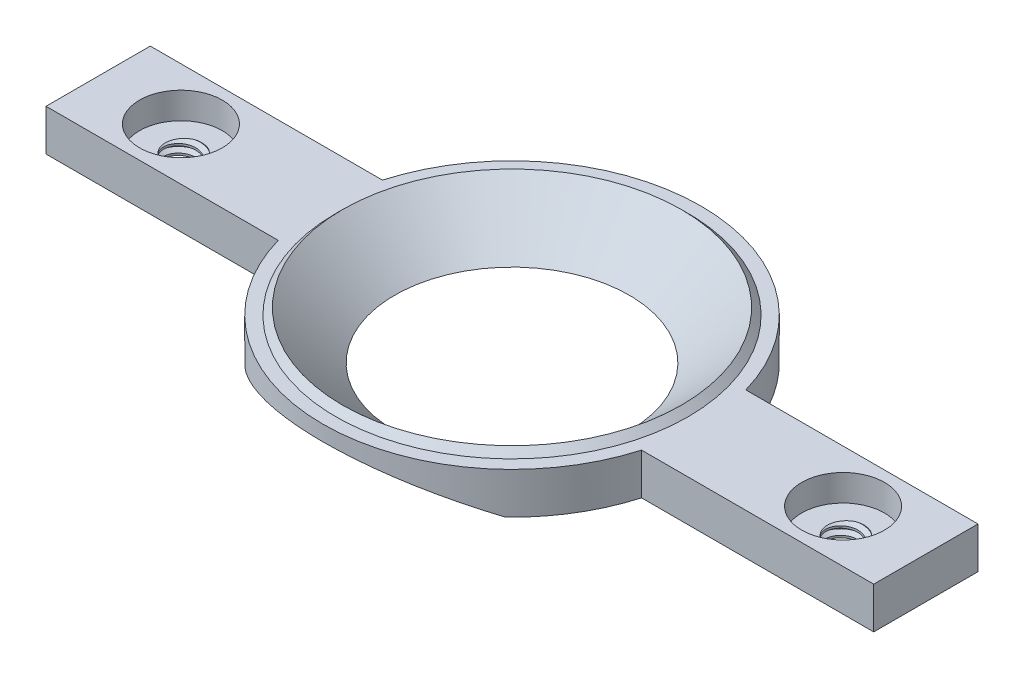
SolidWorks part; units mm, degrees
material "AISI Type 316L stainless steel"
ref_plane "Front Plane" through (0, 0, 0) normal (0, 0, 1) x (1, 0, 0)
ref_plane "Top Plane" through (0, 0, 0) normal (0, 1, 0) x (1, 0, 0)
ref_plane "Right Plane" through (0, 0, 0) normal (1, 0, 0) x (0, 0, -1)
sketch "Sketch1" plane through (0, 0, 0) normal (0, 1, 0) x (1, 0, 0)
  line L0 (0, -1000) -> (0, 49000) construction
  line L1 (-15.875, -2) -> (15.875, -2)
  line L2 (-15.875, -2) -> (-15.875, 2)
  line L3 (-15.875, 2) -> (15.875, 2)
  line L4 (15.875, -2) -> (15.875, 2)
  circle A0 centre (0, 0) radius 7.25
  circle A1 centre (0, 0) radius 6.75
  circle A2 centre (-12.7, 0) radius 0.7937
  circle A4 centre (12.7, 0) radius 0.7937
  point P4 (0, 2)
  point P6 (-15.875, 0)
  dimension "D3" = 14.5
  dimension "D4" = 0.5
  dimension "D5" = 1.5875
  dimension "D6" = 12.7
  dimension "D1" = 31.75
  dimension "D2" = 4
extrude "Boss-Extrude1" add sketch "Sketch1" along normal mid plane 1.5875 contours A0 L3 L2 L1 A2 | A1 L3 A0 L1 | A0 L0 A1 L1 | A1 L0 A0 L3 | L0 A0 L1 A1 | L0 A1 L3 A0 | A0 L1 L4 L3 A4 | A1 L1 A0 L3 region at (-4.31, 0, 5.7209) region at (0.0872, 0, 7) region at (-6.9023, 0, 0) region at (-11.4443, 0, 0) region at (11.4443, 0, 0) region at (6.9023, 0, 0) region at (-4.31, 0, -5.7209) region at (4.31, 0, -5.7209)
sketch "Sketch5" plane through (0, 0, 0) normal (0, 0, 1) x (1, 0, 0)
  line L0 (0, -1000) -> (0, 49000) construction
  line L1 (-6.7568, 0.7937) -> (-6.5, 1.0506)
  line L3 (-6.7568, 0.7937) -> (-6.7568, -0.7937)
  line L4 (-6.7568, -0.7937) -> (-5.0003, -0.7937)
  line L6 (-4.5, -0.7938) -> (-6.7568, -0.7937)
  line L7 (-6.7568, 0.7937) -> (-6.7568, -0.7937)
  line L8 (-4.5, -0.7938) -> (-5.0003, -0.7937)
  line L9 (-6.5, 1.0506) -> (-4.5, -0.7938)
  line L10 (-15.875, -0.7937) -> (-6.9687, -0.7937) construction
  line L11 (-6.7568, -0.7937) -> (-4.5, -0.7938)
  point P7 (-6.7568, 0)
  dimension "D2" = 4.5
  dimension "D3" = 135
  dimension "D4" = 6.5
  dimension "D5" = 0.3632
revolve "Revolve1" add sketch "Sketch5" angle 360 about L0 region at (-5.9861, -0.1318, 0)
sketch "Sketch6" plane through (0, 0, 0) normal (1, 0, 0) x (0, 0, -1)
  line L1 (5.25, -0.7937) -> (7.25, 0.2063)
  line L3 (0, -1000) -> (0, 49000) construction
  line L5 (0, -1000) -> (0, 49000) construction
  line L6 (-7.25, 0.2063) -> (-7.25, -0.7937)
  line L7 (-7.25, -0.7937) -> (-5.25, -0.7937)
  line L8 (-5.25, -0.7937) -> (-7.25, 0.2063)
  line L9 (7.25, -0.7937) -> (5.25, -0.7937)
  line L10 (-7.25, -0.7937) -> (-2, -0.7937) construction
  line L11 (7.25, 0.2063) -> (7.25, -0.7937)
  line L13 (-2, -0.7937) -> (2, -0.7937)
  line L14 (-2, -0.7937) -> (-2, -1.7937)
  line L15 (-2, -1.7937) -> (2, -1.7937)
  line L16 (2, -0.7937) -> (2, -1.7937)
  dimension "D1" = 1
  dimension "D2" = 2
  dimension "D3" = 1
extrude "Cut-Extrude1" cut sketch "Sketch6" along normal up to surface (15.875 mm away) from surface up to face at (15.875, 0, 0) starting at face at (-15.875, 0, 0)
thread "Thread1" pitch 0.3175 method extrude profile "Thread Profile2" start angle 0, offset 0, length 0, pitch 0.3175, diameter 1.5875
ref_plane "Plane2" through (-13.4937, 0.7937, 0) normal (0, 0, 1) x (-1, 0, 0)
sketch "Thread Profile2" plane through (-13.4937, 0.7937, 0) normal (0, 0, 1) x (-1, 0, 0)
  line L0 (0, 0) -> (0, 0.3175) construction
  line L11 (0, 0) -> (0, 0.2778)
  line L12 (0, 0.2778) -> (-0.1719, 0.1786)
  line L13 (-0.1719, 0.1786) -> (-0.1719, 0.0992)
  line L15 (-0.1719, 0.0992) -> (0, 0)
  line L17 (-0.1719, 0.1389) -> (0, 0.1389) construction
  point P2 (0, 0)
  dimension "Pitch" = 0.3175
  dimension "Profile_Angle" = 60
  dimension "Profile_Land" = 0.0794
  dimension "Profile_Height" = 0.1719
thread "Thread2" pitch 0.3175 method extrude profile "Thread Profile3" start angle 0, offset 0, length 0, pitch 0.3175, diameter 1.5875
ref_plane "Plane3" through (11.9062, 0.7937, 0) normal (0, 0, 1) x (-1, 0, 0)
sketch "Thread Profile3" plane through (11.9062, 0.7937, 0) normal (0, 0, 1) x (-1, 0, 0)
  line L0 (0, 0) -> (0, 0.3175) construction
  line L11 (0, 0) -> (0, 0.2778)
  line L12 (0, 0.2778) -> (-0.1719, 0.1786)
  line L13 (-0.1719, 0.1786) -> (-0.1719, 0.0992)
  line L15 (-0.1719, 0.0992) -> (0, 0)
  line L17 (-0.1719, 0.1389) -> (0, 0.1389) construction
  point P2 (0, 0)
  dimension "Pitch" = 0.3175
  dimension "Profile_Angle" = 60
  dimension "Profile_Land" = 0.0794
  dimension "Profile_Height" = 0.1719
sketch "Sketch14" plane through (0, 0.7937, 0) normal (0, 1, 0) x (1, 0, 0)
  line L0 (0, -1.1672) -> (0, 1.1672) construction
  circle A0 centre (12.7, 0) radius 1.5875
  circle A1 centre (-12.7, 0) radius 1.5875
  dimension "D1" = 3.175
extrude "Cut-Extrude2" cut sketch "Sketch14" against normal blind 1.016 contours A1 | A0 body kept at (-6.9687, 0.7937, 2)
